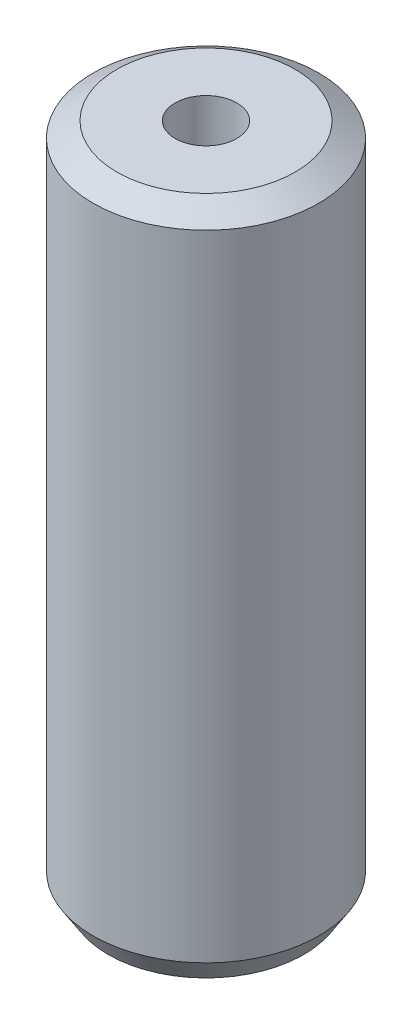
SolidWorks part; units mm, degrees
ref_plane "Front Plane" through (0, 0, 0) normal (0, 0, 1) x (1, 0, 0)
ref_plane "Top Plane" through (0, 0, 0) normal (0, 1, 0) x (1, 0, 0)
ref_plane "Right Plane" through (0, 0, 0) normal (1, 0, 0) x (0, 0, -1)
sketch "Sketch1" plane through (0, 0, 0) normal (0, 1, 0) x (1, 0, 0)
  circle A0 centre (0, 0) radius 15
  dimension "SHAFT_OD" = 30
extrude "Boss-Extrude1" add sketch "Sketch1" along normal blind 89.4947
sketch "Sketch2" plane through (0, 0, 0) normal (0, 1, 0) x (1, 0, 0)
  circle A0 centre (0, 0) radius 4.1003
  dimension "BORE_D" = 8.2006
extrude "Cut-Extrude1" cut sketch "Sketch2" along normal through all
chamfer "Chamfer1" distance 2.0041 angle 57.572 2 edges at (0, 89.4947, 15) (0, 0, 15) first distance on face at (0, 89.4947, 15) first distance on face at (0, 0, 4.1003)
